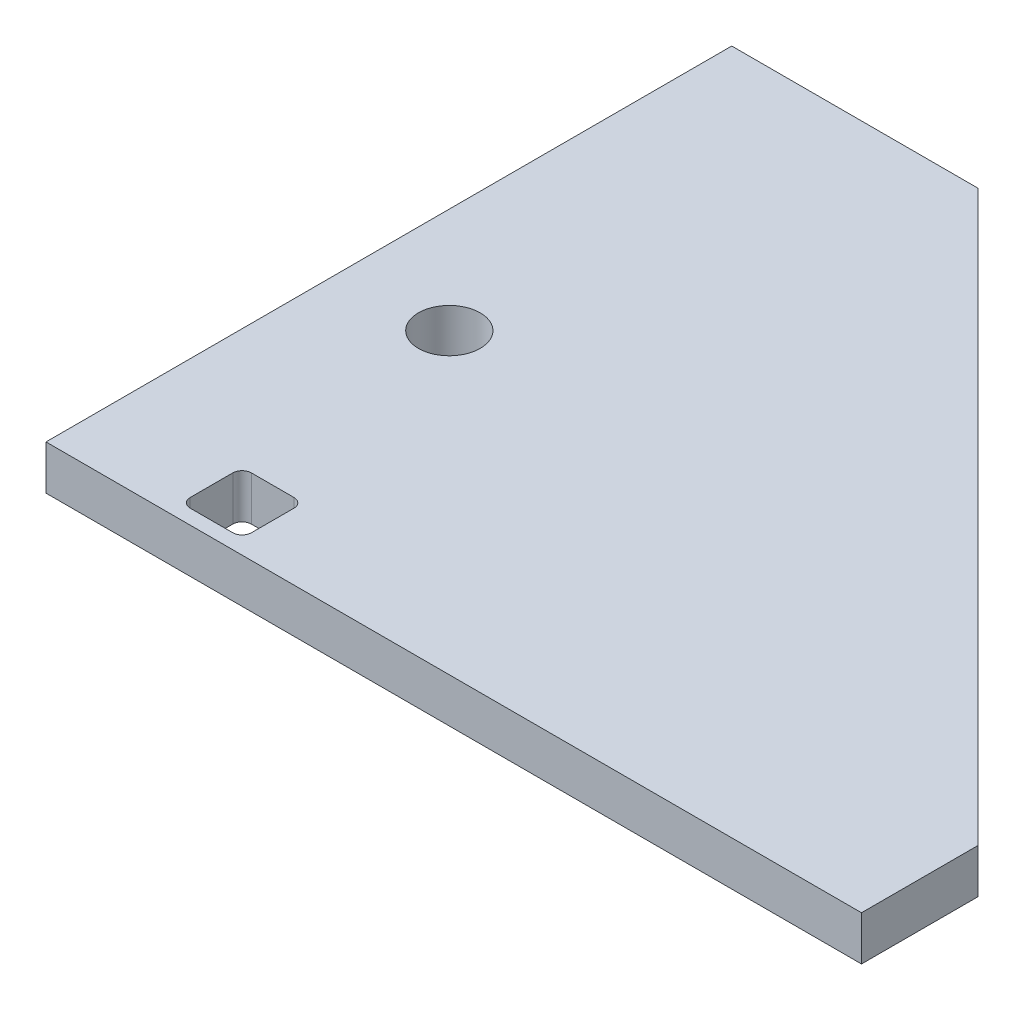
SolidWorks part; units mm, degrees
ref_plane "Front Plane" through (0, 0, 0) normal (0, 0, 1) x (1, 0, 0)
ref_plane "Top Plane" through (0, 0, 0) normal (0, 1, 0) x (1, 0, 0)
ref_plane "Right Plane" through (0, 0, 0) normal (1, 0, 0) x (0, 0, -1)
sketch "Sketch1" plane through (0, 0, 0) normal (0, 1, 0) x (1, 0, 0)
  line L0 (-138.61, 294.305) -> (350, -194.305)
  line L1 (-350, 294.305) -> (-138.61, 294.305)
  line L2 (-350, 294.305) -> (-350, -294.305)
  line L3 (-350, -294.305) -> (350, -294.305)
  line L4 (350, -194.305) -> (350, -294.305)
  line L5 (-350, 294.305) -> (350, -294.305) construction
  point P0 (0, 0)
  dimension "D1" = 588.61
  dimension "D2" = 700
  dimension "D3" = 100
  dimension "D4" = 45
extrude "Boss-Extrude1" add sketch "Sketch1" along normal blind 38.1
sketch "Sketch2" plane through (0, 0, 0) normal (0, -1, 0) x (-1, 0, 0)
  circle A2 centre (259.6468, -38.4802) radius 24.5 construction
  circle A3 centre (259.6468, -38.4802) radius 24.5 construction
  circle A4 centre (259.6468, -38.4802) radius 26.5
  dimension "D1" = 2
extrude "Cut-Extrude1" cut sketch "Sketch2" against normal through all
sketch "Sketch3" plane through (0, 0, 0) normal (0, -1, 0) x (1, 0, 0)
  line L0 (-194.3172, 237.1692) -> (-194.3172, 273.6692)
  line L5 (-202.3172, 281.6692) -> (-238.8172, 281.6692)
  line L6 (-246.8172, 273.6692) -> (-246.8172, 237.1692)
  line L7 (-238.8172, 229.1692) -> (-202.3172, 229.1692)
  line L8 (-196.3172, 237.1692) -> (-196.3172, 273.6692)
  line L9 (-202.3172, 279.6692) -> (-238.8172, 279.6692)
  line L10 (-244.8172, 273.6692) -> (-244.8172, 237.1692)
  line L11 (-238.8172, 231.1692) -> (-202.3172, 231.1692)
  line L12 (-196.3172, 237.1692) -> (-196.3172, 273.6692) construction
  line L13 (-202.3172, 279.6692) -> (-238.8172, 279.6692) construction
  line L14 (-244.8172, 273.6692) -> (-244.8172, 237.1692) construction
  line L15 (-238.8172, 231.1692) -> (-202.3172, 231.1692) construction
  arc A0 (-194.3172, 273.6692) -> (-202.3172, 281.6692) centre (-202.3172, 273.6692) ccw
  arc A1 (-238.8172, 281.6692) -> (-246.8172, 273.6692) centre (-238.8172, 273.6692) ccw
  arc A2 (-246.8172, 237.1692) -> (-238.8172, 229.1692) centre (-238.8172, 237.1692) ccw
  arc A3 (-202.3172, 229.1692) -> (-194.3172, 237.1692) centre (-202.3172, 237.1692) ccw
  arc A4 (-196.3172, 273.6692) -> (-202.3172, 279.6692) centre (-202.3172, 273.6692) ccw
  arc A5 (-238.8172, 279.6692) -> (-244.8172, 273.6692) centre (-238.8172, 273.6692) ccw
  arc A6 (-244.8172, 237.1692) -> (-238.8172, 231.1692) centre (-238.8172, 237.1692) ccw
  arc A7 (-202.3172, 231.1692) -> (-196.3172, 237.1692) centre (-202.3172, 237.1692) ccw
  arc A8 (-196.3172, 273.6692) -> (-202.3172, 279.6692) centre (-202.3172, 273.6692) ccw construction
  arc A9 (-238.8172, 279.6692) -> (-244.8172, 273.6692) centre (-238.8172, 273.6692) ccw construction
  arc A10 (-244.8172, 237.1692) -> (-238.8172, 231.1692) centre (-238.8172, 237.1692) ccw construction
  arc A11 (-202.3172, 231.1692) -> (-196.3172, 237.1692) centre (-202.3172, 237.1692) ccw construction
  dimension "D1" = 0
  dimension "D2" = 2
extrude "Cut-Extrude2" cut sketch "Sketch3" against normal through all
